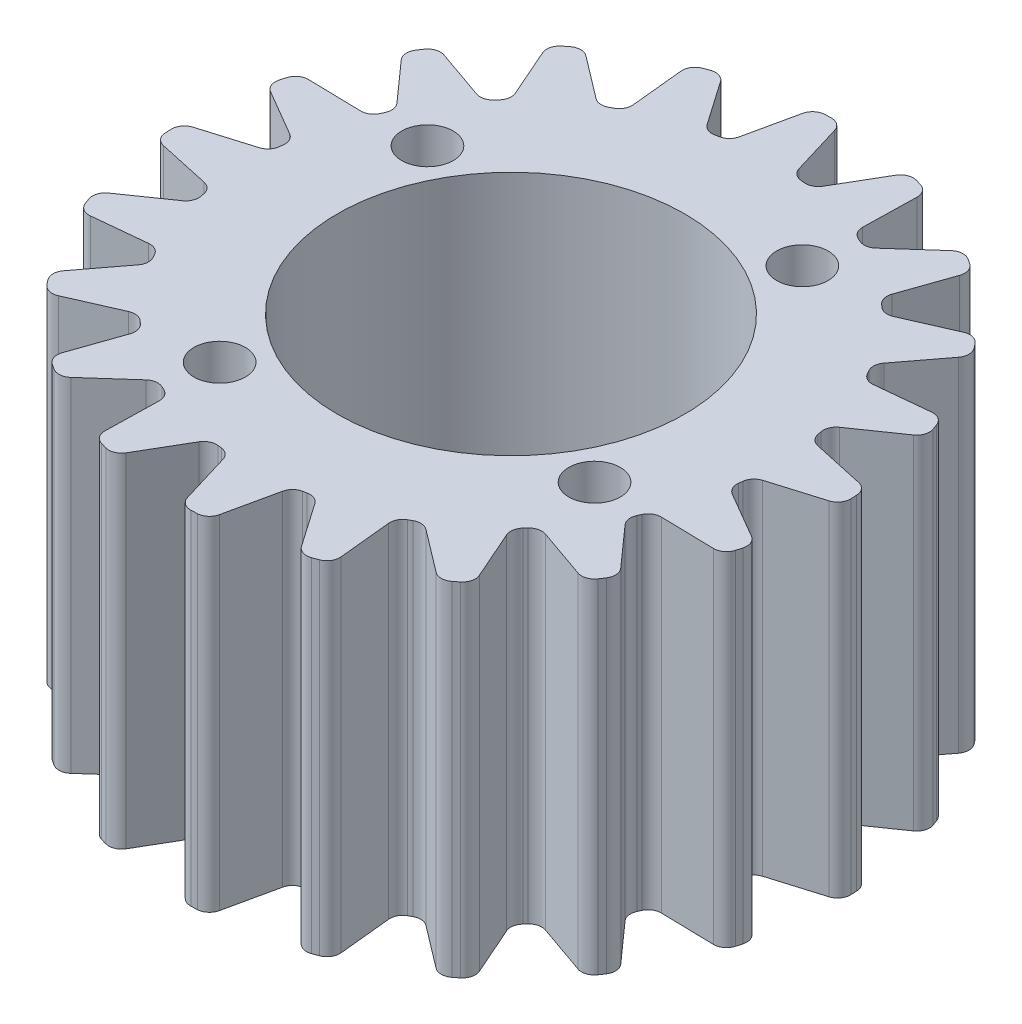
SolidWorks part; units mm, degrees
note: '?' marks a value the reader was unsure of.
ref_plane "Plan de face" through (0, 0, 0) normal (0, 0, 1) x (1, 0, 0)
ref_plane "Plan de dessus" through (0, 0, 0) normal (0, 1, 0) x (1, 0, 0)
ref_plane "Plan de droite" through (0, 0, 0) normal (1, 0, 0) x (0, 0, -1)
sketch "Esquisse1" plane through (0, 0, 0) normal (0, 0, 1) x (1, 0, 0)
  line L0 (-77, 80) -> (-77, 0)
  line L1 (-70, 80) -> (0, 80)
  line L2 (0, 80) -> (0, 0)
  line L3 (0, 80) -> (0, 0) construction
  line L4 (0, 0) -> (-70, 0)
  line L18 (-77, 80) -> (-70, 80)
  line L19 (-70, 80) -> (-70, 0) construction
  line L20 (-70, 0) -> (-77, 0)
  dimension "D2" = 80
  dimension "D3" = 77
  dimension "D15" = 70
revolve "Révolution1" add sketch "Esquisse1" angle 360 about L3
sketch "Esquisse5" plane through (0, 80, 0) normal (0, 1, 0) x (1, 0, 0)
  line L0 (0, 0) -> (0, 77) construction
  line L1 (0, 0) -> (-23.7943, 73.2314) construction
  line L2 (-23.7943, 73.2314) -> (-14.2985, 59.5577)
  line L3 (-14.2985, 59.5577) -> (-9.5816, 60.4959)
  line L4 (-9.5816, 60.4959) -> (-6.0414, 76.7626)
  line L5 (-6.0414, 76.7626) -> (0, 77)
  line L6 (-6.0414, 76.7626) -> (0, 0) construction
  line L7 (-9.5816, 60.4959) -> (0, 0) construction
  line L8 (-14.2985, 59.5577) -> (0, 0) construction
  line L9 (0, 77) -> (0, 108.0563)
  line L10 (0, 108.0563) -> (-32.7745, 100.2719)
  line L11 (-32.7745, 100.2719) -> (-23.7943, 73.2314)
  circle A0 centre (0, 0) radius 77 construction
  circle A1 centre (0, 0) radius 61.25 construction
  circle A2 centre (0, 0) radius 77 construction
  dimension "D1" = 18
  dimension "D2" = 4.5
  dimension "D3" = 4.5
  dimension "D5" = 122.5
  dimension "D4" = 4.5
extrude "Enlèv. mat.-Extru.3" cut sketch "Esquisse5" against normal through all
fillet "Congé1" radius 3 4 edges at (-23.7943, 40, -73.2314) (-6.0414, 40, -76.7626) (-14.2985, 40, -59.5577) (-9.5816, 40, -60.4959)
ref_axis "Axe1" through (0, 39.3, 0) along (0, -1, 0)?
pattern_circular "Répétition circulaire1" count 20 over 360 about axis through (0, 0, 0) along (0, 1, 0) of "Enlèv. mat.-Extru.3", "Congé1"
sketch "Esquisse6" plane through (0, 80, 0) normal (0, 1, 0) x (1, 0, 0)
  line L0 (0, 0) -> (0, -49.9924) construction
  line L1 (-40.5, 0) -> (40.5, 0) construction
  line L3 (0, 0) -> (11.1633, -38.9311) construction
  line L4 (0, 0) -> (-24.2368, -43.7244) construction
  circle A0 centre (0, 0) radius 40.5
  circle A1 centre (-43.7244, 24.2368) radius 6
  circle A2 centre (0, 0) radius 49.9924 construction
  circle A3 centre (-24.2368, -43.7244) radius 6
  circle A4 centre (-13.9809, 90.8751) radius 6
  circle A5 centre (24.2368, 43.7244) radius 6
  circle A6 centre (43.7244, -24.2368) radius 6
  point P17 (21.3691, 55.5251)
  point P23 (0, 0)
  dimension "D3" = 12
  dimension "D1" = 4
  dimension "D2" = 81
  dimension "D6" = 99.9849
  dimension "D4" = 45
  dimension "D5" = 70.7
  dimension "D7" = 16
extrude "Enlèv. mat.-Extru.4" cut sketch "Esquisse6" against normal through all
